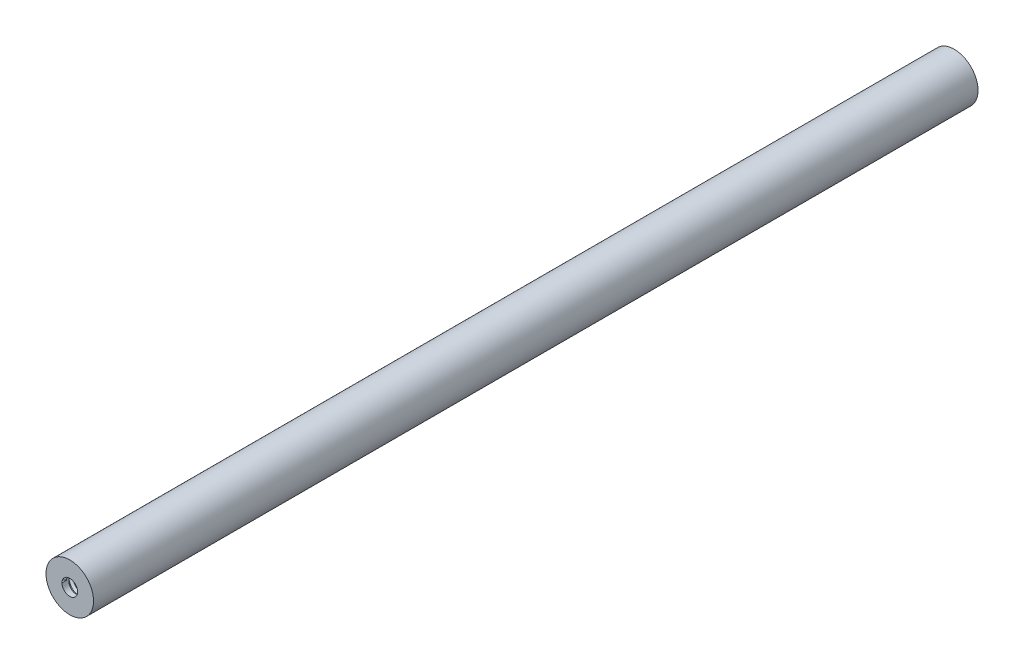
SolidWorks part; units mm, degrees
material "Acciaio al carbonio semplice"
ref_plane "Front" through (0, 0, 0) normal (0, 0, 1) x (1, 0, 0)
ref_plane "Top" through (0, 0, 0) normal (0, 1, 0) x (1, 0, 0)
ref_plane "Right" through (0, 0, 0) normal (1, 0, 0) x (0, 0, -1)
sketch "Schizzo1" plane through (0, 0, 0) normal (0, 0, 1) x (1, 0, 0)
  circle A0 centre (0, 0) radius 5
  dimension "D1" = 10
extrude "Estrusione-Estrusione1" add sketch "Schizzo1" along normal mid plane 186
hole_wizard "Foro filettato M4-1" positions "Schizzo2" profile "Schizzo3" tap size "M4" standard "ISO"
sketch "Schizzo2" plane through (0, 0, 93) normal (0, 0, 1) x (1, 0, 0)
  point P0 (0, 0)
sketch "Schizzo3" plane through (0, 0, 93) normal (1, 0, 0) x (0, -1, 0)
  line L0 (0, 0) -> (0, 16.4914)
  line L1 (0, 16.4914) -> (1.65, 15.5)
  line L2 (1.65, 15.5) -> (1.65, 0)
  line L5 (1.65, 0) -> (0, 0)
  line L10 (0, 16.4914) -> (-1.65, 15.5) construction
  line L11 (0, -6.35) -> (0, 107.95) construction
  dimension "Tap Drill Dia." = 3.3
  dimension "Tap Drill Depth" = 15.5
  dimension "Drill Angle" = 118
cosmetic thread "Filettatura del foro1" parameters "D1"=12, "D2"=4
hole_wizard "Foro filettato M4-2" positions "Schizzo4" profile "Schizzo5" tap size "M4" standard "ISO"
sketch "Schizzo4" plane through (0, 0, -93) normal (0, 0, -1) x (-1, 0, 0)
  point P0 (0, 0)
sketch "Schizzo5" plane through (0, 0, -93) normal (1, 0, 0) x (0, 1, 0)
  line L0 (0, 0) -> (0, 16.4914)
  line L1 (0, 16.4914) -> (1.65, 15.5)
  line L2 (1.65, 15.5) -> (1.65, 0)
  line L5 (1.65, 0) -> (0, 0)
  line L10 (0, 16.4914) -> (-1.65, 15.5) construction
  line L11 (0, -6.35) -> (0, 107.95) construction
  dimension "Tap Drill Dia." = 3.3
  dimension "Tap Drill Depth" = 15.5
  dimension "Drill Angle" = 118
cosmetic thread "Filettatura del foro2" parameters "D1"=12, "D2"=4
thread "螺纹线1" pitch 1.0583 method cut profile "螺纹线轮廓1" start angle 0, offset 0, length 14.3, pitch 1.4583, diameter 3.3
ref_plane "基准面1" through (1.65, 0, -93) normal (0, 1, 0) x (-1, 0, 0)
sketch "螺纹线轮廓1" plane through (1.65, 0, -93) normal (0, 1, 0) x (-1, 0, 0)
  line L0 (0, 0) -> (0, 1.0583) construction
  line L11 (0, 0) -> (0, 0.926)
  line L12 (0, 0.926) -> (-0.5728, 0.5953)
  line L13 (-0.5728, 0.5953) -> (-0.5728, 0.3307)
  line L15 (-0.5728, 0.3307) -> (0, 0)
  line L17 (-0.5728, 0.463) -> (0, 0.463) construction
  point P2 (0, 0)
  dimension "Pitch" = 1.0583
  dimension "Profile_Angle" = 60
  dimension "Profile_Land" = 0.2646
  dimension "Profile_Height" = 0.5728
thread "螺纹线2" pitch 1.0583 method cut profile "螺纹线轮廓2" start angle 0, offset 0, length 14.3, pitch 1.4583, diameter 3.3
ref_plane "基准面2" through (-1.65, 0, 93) normal (0, 1, 0) x (1, 0, 0)
sketch "螺纹线轮廓2" plane through (-1.65, 0, 93) normal (0, 1, 0) x (1, 0, 0)
  line L0 (0, 0) -> (0, 1.0583) construction
  line L11 (0, 0) -> (0, 0.926)
  line L12 (0, 0.926) -> (-0.5728, 0.5953)
  line L13 (-0.5728, 0.5953) -> (-0.5728, 0.3307)
  line L15 (-0.5728, 0.3307) -> (0, 0)
  line L17 (-0.5728, 0.463) -> (0, 0.463) construction
  point P2 (0, 0)
  dimension "Pitch" = 1.0583
  dimension "Profile_Angle" = 60
  dimension "Profile_Land" = 0.2646
  dimension "Profile_Height" = 0.5728
